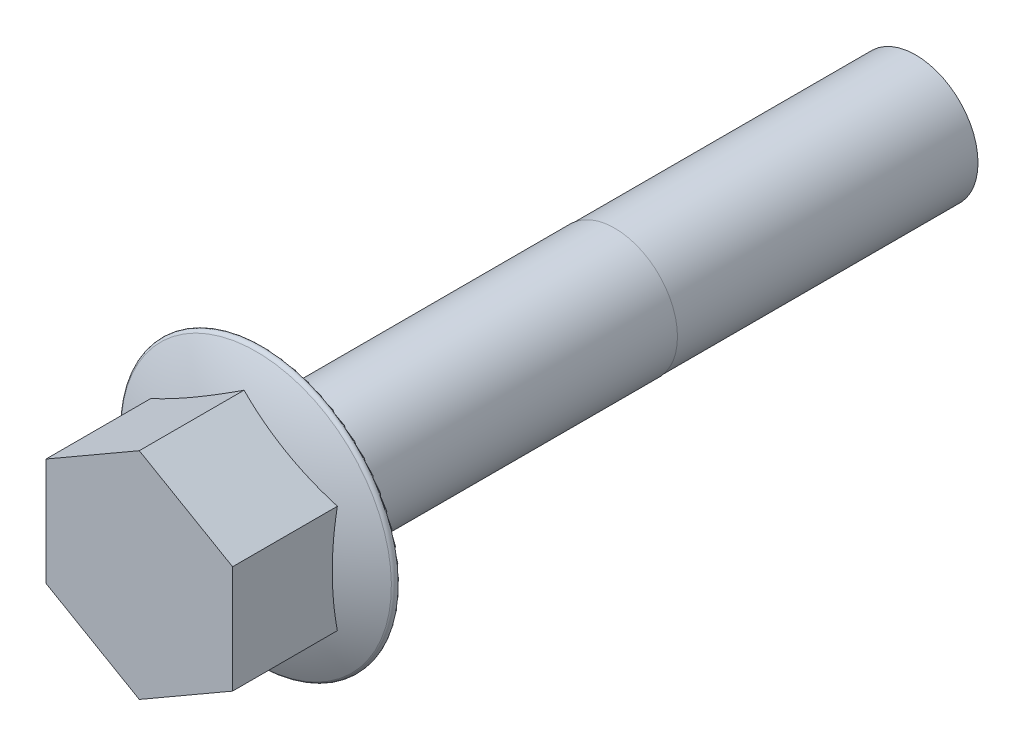
SolidWorks part; units mm, degrees
note: '?' marks a value the reader was unsure of.
ref_plane "Plane1" through (0, 0, 0) normal (0, 0, 1) x (1, 0, 0)
ref_plane "Plane2" through (0, 0, 0) normal (0, 1, 0) x (-1, 0, 0)
ref_plane "Plane3" through (0, 0, 0) normal (1, 0, 0) x (0, 0, -1)
sketch "Head Sketch" plane through (0, 0, 0) normal (0, 0, 1) x (1, 0, 0)
  line L0 (0, 13.6382) -> (11.811, 6.8191)
  line L1 (11.811, 6.8191) -> (11.811, -6.8191)
  line L2 (11.811, -6.8191) -> (0, -13.6382)
  line L3 (0, -13.6382) -> (-11.811, -6.8191)
  line L4 (-11.811, -6.8191) -> (-11.811, 6.8191)
  line L5 (-11.811, 6.8191) -> (0, 13.6382)
  line L6 (11.811, 6.8191) -> (-11.811, -6.8191) construction
  line L7 (0, 13.6382) -> (0, -13.6382) construction
  line L8 (-11.811, 6.8191) -> (11.811, -6.8191) construction
  point P0 (0, 0)
  dimension "D1" = 60
  dimension "D2" = 60
  dimension "Width across flats" = 23.622
extrude "Head" add sketch "Head Sketch" along normal blind 15.748
sketch "Shank Sketch" plane through (0, 0, 0) normal (0, 0, 1) x (1, 0, 0)
  line L0 (50, 0) -> (-50, 0) construction
  line L1 (0, -50) -> (0, 50) construction
  circle A0 centre (0, 0) radius 7.9375
  dimension "Shank diameter" = 15.875
extrude "Shank" add sketch "Shank Sketch" against normal blind 82.55
sketch "Sketch3" plane through (0, 0, 0) normal (0, 1, 0) x (-1, 0, 0)
  line L0 (0, 0) -> (0, 10) construction
  line L1 (0, -82.55) -> (0, 0) construction
  line L4 (-16.891, 0) -> (0, 0)
  line L5 (0, 0) -> (0, 5)
  arc A0 (0, 5) -> (-17.1152, 0.9469) centre (0, -33.1632) ccw
  arc A1 (-16.891, 0) -> (-17.1152, 0.9469) centre (-16.891, 0.5) cw
  dimension "D1" = 0.5
  dimension "D2" = 33.782
  dimension "D3" = 5
revolve "Flange" add sketch "Sketch3" angle 360 about L0
ref_axis "Axis1" through (0, 0, -132.55) along (0, 0, 1)?
sketch "Thread End" plane through (0, 0, 0) normal (1, 0, 0) x (0, 0, -1)
  line L0 (44.45, 7.9375) -> (44.45, 7.8875)
  line L2 (44.45, 7.8875) -> (82.55, 7.8875)
  line L3 (82.55, 7.9375) -> (44.45, 7.9375)
  line L4 (21.5519, 0) -> (27.4271, 0) construction
  line L5 (82.55, 0) -> (0, 0) construction
  line L6 (82.55, -7.9375) -> (82.55, 7.9375) construction
  line L7 (82.55, 7.8875) -> (82.55, 7.9375)
  dimension "D1" = 0.05
  dimension "Length of thread" = 38.1
revolve "Thread Cut" cut sketch "Thread End" angle 360 about L4
cosmetic thread "Cosmetic Thread2" parameters "D2"=11
